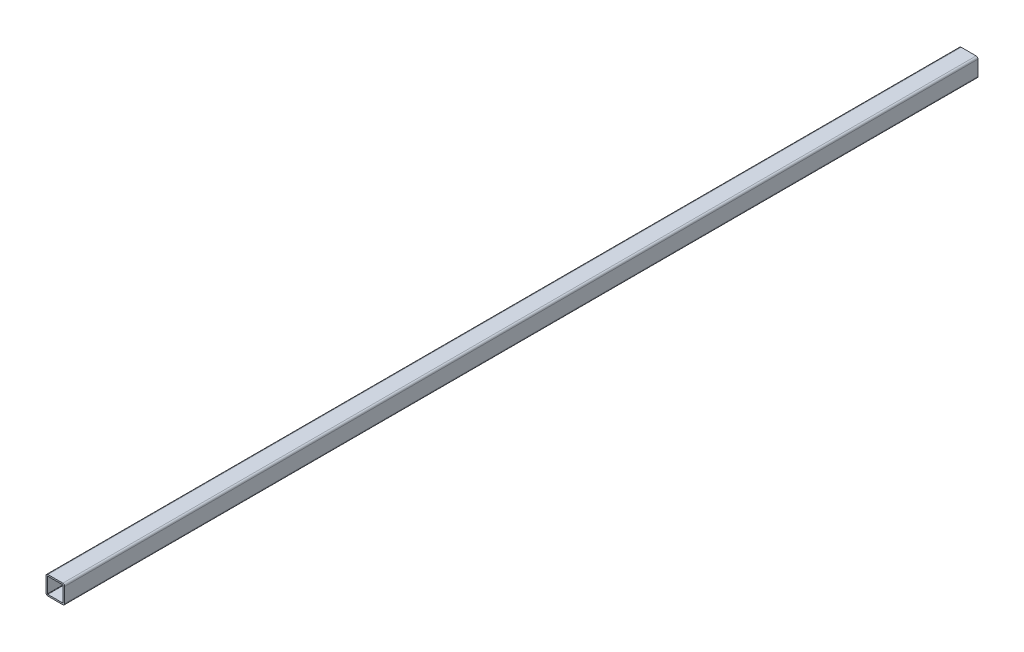
SolidWorks part; units mm, degrees
ref_plane "Front Plane" through (0, 0, 0) normal (0, 0, 1) x (1, 0, 0)
ref_plane "Top Plane" through (0, 0, 0) normal (0, 1, 0) x (1, 0, 0)
ref_plane "Right Plane" through (0, 0, 0) normal (1, 0, 0) x (0, 0, -1)
sketch "Sketch1" plane through (0, 0, 0) normal (0, 0, 1) x (1, 0, 0)
  line L1 (10, -12.5) -> (-10, -12.5)
  line L2 (12.5, -10) -> (12.5, 10)
  line L3 (10, 12.5) -> (-10, 12.5)
  line L4 (-12.5, -10) -> (-12.5, 10)
  line L5 (12.5, -12.5) -> (-12.5, 12.5) construction
  line L6 (12.5, 12.5) -> (-12.5, -12.5) construction
  arc A0 (-10, 12.5) -> (-12.5, 10) centre (-10, 10) ccw
  arc A1 (12.5, 10) -> (10, 12.5) centre (10, 10) ccw
  arc A2 (10, -12.5) -> (12.5, -10) centre (10, -10) ccw
  arc A3 (-10, -12.5) -> (-12.5, -10) centre (-10, -10) cw
  point P0 (0, 0)
  point P18 (0, 0)
  dimension "D2" = 2.5
  dimension "D1" = 25
extrude "Extrude-Thin1" add sketch "Sketch1" along normal mid plane 1219.2 thin thin type one direction reverse wall 2
equation "\"D2@Sketch1\" = \"D5@Extrude-Thin1\" * 1.25"
